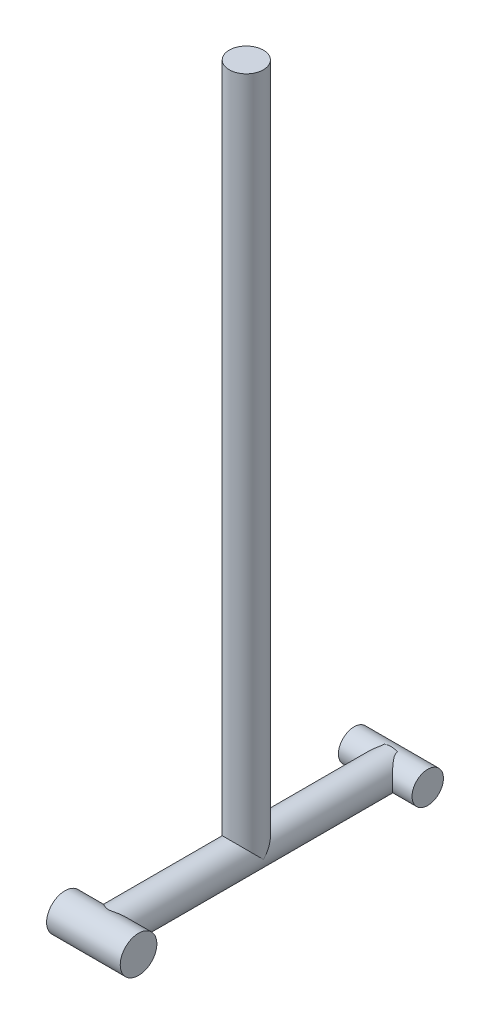
SolidWorks part; units mm, degrees
ref_plane "Front Plane" through (0, 0, 0) normal (0, 0, 1) x (1, 0, 0)
ref_plane "Top Plane" through (0, 0, 0) normal (0, 1, 0) x (1, 0, 0)
ref_plane "Right Plane" through (0, 0, 0) normal (1, 0, 0) x (0, 0, -1)
sketch "Sketch1" plane through (0, 0, 0) normal (0, 0, 1) x (1, 0, 0)
  line L0 (0, 708.66) -> (0, -708.66) construction
  line L1 (-101.6, 4072.636) -> (101.6, 4072.636)
  line L2 (-101.6, 4072.636) -> (-101.6, 0)
  line L3 (-101.6, 0) -> (101.6, 0)
  line L4 (101.6, 4072.636) -> (101.6, 0)
  line L5 (0, 0) -> (0, 4072.636)
  point P4 (0, 0)
  point P8 (0, 0)
  dimension "D1" = 1417.32
  dimension "D2" = 4781.296
  dimension "D3" = 203.2
revolve "Revolve3" add sketch "Sketch1" angle 360 about L5 region at (-50.8, 2036.318, 0)
sketch "Sketch2" plane through (0, 0, 0) normal (1, 0, 0) x (0, 0, -1)
  line L0 (-861.06, 0) -> (861.06, 0)
  line L1 (-861.06, 101.6) -> (861.06, 101.6)
  line L2 (-861.06, 101.6) -> (-861.06, -101.6)
  line L3 (-861.06, -101.6) -> (861.06, -101.6)
  line L4 (861.06, 101.6) -> (861.06, -101.6)
  point P6 (0, 0)
  dimension "D1" = 1722.12
  dimension "D2" = 203.2
revolve "Revolve4" add sketch "Sketch2" angle 360 about L0 region at (0, 50.8, 0)
sketch "Sketch3" plane through (0, 0, 0) normal (0, 1, 0) x (1, 0, 0)
  line L0 (101.6, 861.06) -> (-101.6, 861.06) construction
  line L1 (-625.5967, 861.06) -> (625.5967, 861.06) construction
  line L2 (-625.5967, 861.06) -> (-625.5967, -861.06) construction
  line L3 (-625.5967, -861.06) -> (625.5967, -861.06) construction
  line L4 (625.5967, 861.06) -> (625.5967, -861.06) construction
  line L5 (-101.6, -861.06) -> (101.6, -861.06) construction
  line L6 (-625.5967, 861.06) -> (625.5967, -861.06) construction
  line L7 (-219.1967, -861.06) -> (219.1967, -861.06)
  line L8 (-219.1967, 954.5508) -> (219.1967, 954.5508)
  line L9 (-219.1967, 954.5508) -> (-219.1967, 767.5692)
  line L10 (-219.1967, 767.5692) -> (219.1967, 767.5692)
  line L11 (219.1967, 954.5508) -> (219.1967, 767.5692)
  line L12 (-219.1967, -751.9874) -> (219.1967, -751.9874)
  line L13 (-219.1967, -751.9874) -> (-219.1967, -970.1326)
  line L14 (-219.1967, -970.1326) -> (219.1967, -970.1326)
  line L15 (219.1967, -751.9874) -> (219.1967, -970.1326)
  line L16 (-219.1967, 861.06) -> (219.1967, 861.06)
  point P6 (0, -861.06)
  point P22 (0, 861.06)
  point P23 (0, -861.06)
  point P24 (0, 0)
  dimension "D1" = 36
  dimension "D2" = 406.4
revolve "Revolve7" add sketch "Sketch3" angle 360 about L16 region at (0, 0, -907.8054)
revolve "Revolve9" add sketch "Sketch3<4>" angle 360 about L7 region at (0, 0, 915.5963)
sketch "Sketch3<4>" plane through (0, 0, 0) normal (0, 1, 0) x (1, 0, 0) same geometry as "Sketch3"
